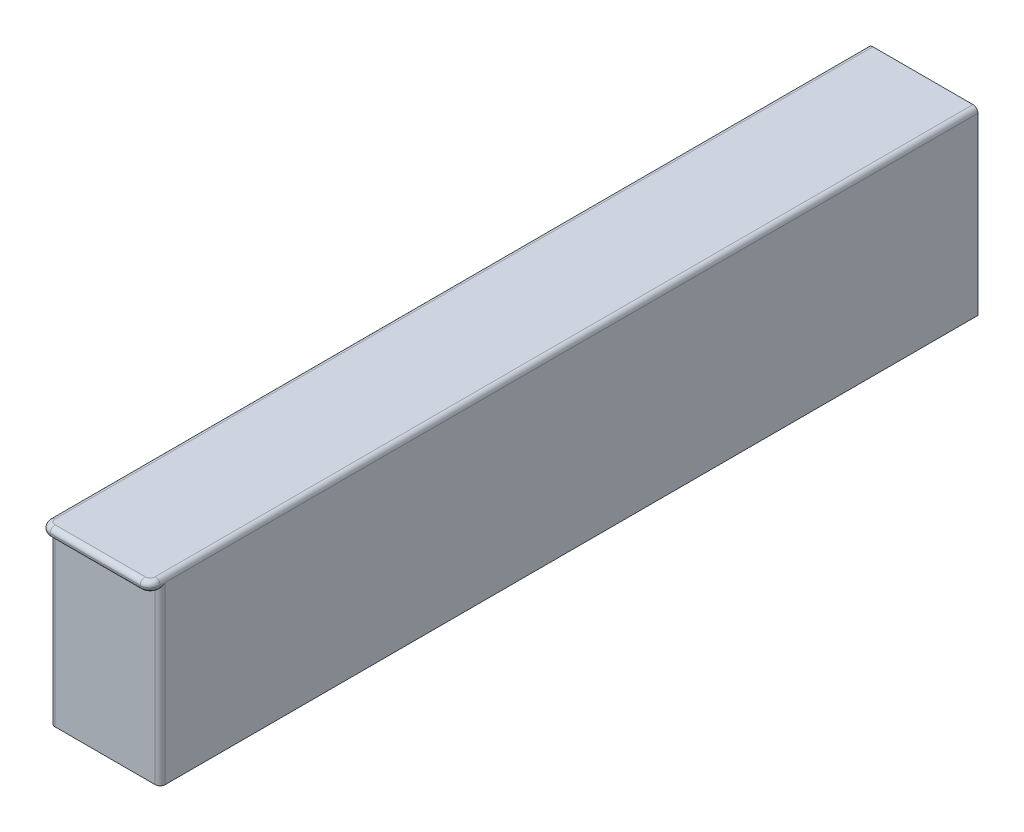
SolidWorks part; units mm, degrees
ref_plane "Front Plane" through (0, 0, 0) normal (0, 0, 1) x (1, 0, 0)
ref_plane "Top Plane" through (0, 0, 0) normal (0, 1, 0) x (1, 0, 0)
ref_plane "Right Plane" through (0, 0, 0) normal (1, 0, 0) x (0, 0, -1)
sketch "Sketch1" plane through (0, 0, 0) normal (0, 1, 0) x (1, 0, 0)
  line L1 (-11, -81.75) -> (11, -81.75)
  line L2 (-11, -81.75) -> (-11, 81.75)
  line L3 (-11, 81.75) -> (11, 81.75)
  line L4 (11, -81.75) -> (11, 81.75)
  line L5 (-11, -81.75) -> (11, 81.75) construction
  line L6 (-11, 81.75) -> (11, -81.75) construction
  point P0 (0, 0)
  dimension "D1" = 163.5
  dimension "D2" = 22
extrude "Boss-Extrude1" add sketch "Sketch1" along normal blind 36 contours L2 L3 L4 L1
fillet "Fillet1" radius 1 2 edges at (-11, 18, 81.75) (11, 18, 81.75)
sketch "Sketch2" plane through (0, 36, 0) normal (0, 1, 0) x (1, 0, 0)
  line L0 (11, -80.75) -> (11, 81.75) construction
  line L1 (-11, 81.75) -> (11, 81.75)
  line L2 (-11, 81.75) -> (-11, -83.75)
  line L3 (-11, -83.75) -> (11, -83.75)
  line L4 (11, 81.75) -> (11, -83.75)
  line L5 (-10, -81.75) -> (10, -81.75) construction
  dimension "D1" = 2
extrude "Boss-Extrude2" add sketch "Sketch2" against normal blind 2
fillet "Fillet2" radius 2 2 edges at (-11, 35, 83.75) (11, 35, 83.75)
fillet "Fillet3" radius 1 10 edges at (-11, 34, 81.25) (-10.4142, 34, 83.1642) (11, 34, 81.25) (10.4142, 34, 83.1642) (11, 36, 0) (10.4142, 36, 83.1642) (0, 36, 83.75) (-10.4142, 36, 83.1642) (-11, 36, 0) (0, 34, 83.75)
sketch "Sketch3" plane through (0, 36, 0) normal (0, 1, 0) x (1, 0, 0)
  line L1 (7.5, -31.75) -> (11, -31.75)
  line L2 (7.5, -31.75) -> (7.5, 81.75)
  line L3 (7.5, 81.75) -> (11, 81.75)
  line L4 (11, -31.75) -> (11, 81.75)
  line L5 (7.5, -31.75) -> (11, 81.75) construction
  line L6 (7.5, 81.75) -> (11, -31.75) construction
  line L7 (-10, -81.75) -> (10, -81.75) construction
  line L8 (-11, 81.75) -> (11, 81.75) construction
  line L9 (11, 81.75) -> (11, -80.75) construction
  dimension "D1" = 3.5
  dimension "D2" = 50
extrude "Cut-Extrude2" [suppressed] cut sketch "Sketch3" against normal through all
sketch "Sketch5" plane through (-11, 0, 0) normal (-1, 0, 0) x (0, 0, 1)
  line L0 (81.75, 34) -> (81.75, 0) construction
  line L1 (80.75, 0) -> (-81.75, 0) construction
  line L2 (-81.75, 36) -> (81.75, 36) construction
  line L3 (-81.75, 35) -> (-81.75, 0) construction
  line L8 (31.75, 36) -> (-81.75, 36)
  line L9 (31.75, 0) -> (31.75, 36)
  line L10 (-81.75, 0) -> (31.75, 0)
  line L11 (-81.75, 36) -> (-81.75, 0)
  dimension "D1" = 50
extrude "Cut-Extrude4" [suppressed] cut sketch "Sketch5" against normal blind 3.5
sketch "Sketch4" [suppressed] plane through (7.5, 0, 0) normal (1, 0, 0) x (0, 0, -1)
  line L4 (81.75, 36) -> (-31.75, 36)
  line L5 (-31.75, 36) -> (-31.75, 0)
  line L6 (-31.75, 0) -> (81.75, 0)
  line L7 (81.75, 0) -> (81.75, 36)
  line L8 (81.75, 36) -> (-31.75, 36)
  line L9 (-31.75, 36) -> (-31.75, 0)
  line L10 (-31.75, 0) -> (81.75, 0)
  line L11 (81.75, 0) -> (81.75, 36)
  dimension "D1" = 0
extrude "Cut-Extrude3" [suppressed] cut sketch "Sketch4" against normal blind 3.25
sketch "Sketch6" [suppressed] plane through (-7.5, 0, 0) normal (-1, 0, 0) x (0, 0, 1)
  line L4 (-81.75, 36) -> (-81.75, 0)
  line L5 (-81.75, 0) -> (31.75, 0)
  line L6 (31.75, 0) -> (31.75, 36)
  line L7 (31.75, 36) -> (-81.75, 36)
  line L8 (-81.75, 36) -> (-81.75, 0)
  line L9 (-81.75, 0) -> (31.75, 0)
  line L10 (31.75, 0) -> (31.75, 36)
  line L11 (31.75, 36) -> (-81.75, 36)
  dimension "D1" = 0
extrude "Cut-Extrude5" [suppressed] cut sketch "Sketch6" against normal blind 3.25
sketch "White" plane through (0, 0, 0) normal (0, 1, 0) x (1, 0, 0)
  line L0 (12.5, -81.75) -> (34.5, -81.75)
  line L1 (-11, -81.75) -> (11, -81.75)
  line L2 (-11, -81.75) -> (-11, 81.75)
  line L3 (-11, 81.75) -> (11, 81.75)
  line L4 (11, -81.75) -> (11, 81.75)
  line L5 (12.5, -81.75) -> (12.5, 81.75)
  line L6 (12.5, 81.75) -> (34.5, 81.75)
  line L7 (34.5, -81.75) -> (34.5, 81.75)
  line L8 (36, -81.75) -> (58, -81.75)
  line L9 (36, -81.75) -> (36, 81.75)
  line L10 (36, 81.75) -> (58, 81.75)
  line L11 (58, -81.75) -> (58, 81.75)
  line L12 (59.5, -81.75) -> (81.5, -81.75)
  line L13 (59.5, -81.75) -> (59.5, 81.75)
  line L14 (59.5, 81.75) -> (81.5, 81.75)
  line L15 (81.5, -81.75) -> (81.5, 81.75)
  line L16 (83, -81.75) -> (105, -81.75)
  line L17 (83, -81.75) -> (83, 81.75)
  line L18 (83, 81.75) -> (105, 81.75)
  line L19 (105, -81.75) -> (105, 81.75)
  line L20 (106.5, -81.75) -> (128.5, -81.75)
  line L21 (106.5, -81.75) -> (106.5, 81.75)
  line L22 (106.5, 81.75) -> (128.5, 81.75)
  line L23 (128.5, -81.75) -> (128.5, 81.75)
  line L24 (130, -81.75) -> (152, -81.75)
  line L25 (130, -81.75) -> (130, 81.75)
  line L26 (130, 81.75) -> (152, 81.75)
  line L27 (152, -81.75) -> (152, 81.75)
  dimension "D1" = 7
sketch "Black" plane through (0, 0, 0) normal (0, 1, 0) x (1, 0, 0)
  line L0 (-11, 81.75) -> (11, 81.75) construction
  line L1 (16, -31.75) -> (4, -31.75)
  line L2 (16, -31.75) -> (16, 81.75)
  line L3 (16, 81.75) -> (4, 81.75)
  line L4 (4, -31.75) -> (4, 81.75)
  line L6 (31, -31.75) -> (43, -31.75)
  line L7 (31, -31.75) -> (31, 81.75)
  line L8 (31, 81.75) -> (43, 81.75)
  line L9 (43, -31.75) -> (43, 81.75)
  line L10 (12.5, -81.75) -> (34.5, -81.75) construction
  line L11 (16, -31.75) -> (31, -31.75) construction
  line L12 (36, 81.75) -> (58, 81.75) construction
  line L13 (106.5, 81.75) -> (128.5, 81.75) construction
  line L14 (111.75, 81.75) -> (99.75, 81.75)
  line L15 (111.75, 81.75) -> (111.75, -31.75)
  line L16 (111.75, -31.75) -> (99.75, -31.75)
  line L17 (99.75, 81.75) -> (99.75, -31.75)
  line L18 (83, 81.75) -> (105, 81.75) construction
  line L19 (126.75, 81.75) -> (138.75, 81.75)
  line L20 (126.75, 81.75) -> (126.75, -31.75)
  line L21 (126.75, -31.75) -> (138.75, -31.75)
  line L22 (138.75, 81.75) -> (138.75, -31.75)
  line L23 (84.75, 81.75) -> (72.75, 81.75)
  line L24 (84.75, 81.75) -> (84.75, -31.75)
  line L25 (84.75, -31.75) -> (72.75, -31.75)
  line L26 (72.75, 81.75) -> (72.75, -31.75)
  line L27 (105, -81.75) -> (106.5, -81.75) construction
  point P14 (23.5, -81.75)
  point P15 (23.5, -31.75)
  point P36 (105.75, -81.75)
  point P37 (105.75, -31.75)
  dimension "D1" = 50
  dimension "D2" = 12
  dimension "D3" = 12
  dimension "D4" = 15
  dimension "D5" = 15
  dimension "D6" = 15
sketch "Sketch11" plane through (0, 36, 0) normal (0, 1, 0) x (1, 0, 0)
  line L1 (11, 81.75) -> (2.5, 81.75)
  line L2 (11, 81.75) -> (11, -31.75)
  line L3 (11, -31.75) -> (2.5, -31.75)
  line L4 (2.5, 81.75) -> (2.5, -31.75)
  line L5 (16, -31.75) -> (4, -31.75) construction
  dimension "D1" = 8.5
extrude "C" [suppressed] cut sketch "Sketch11" against normal through all
sketch "Sketch12" plane through (0, 36, 0) normal (0, 1, 0) x (1, 0, 0)
  line L0 (31, -31.75) -> (43, -31.75) construction
  line L1 (-11, 81.75) -> (-6, 81.75)
  line L2 (-11, 81.75) -> (-11, -31.75)
  line L3 (-11, -31.75) -> (-6, -31.75)
  line L4 (-6, 81.75) -> (-6, -31.75)
  line L5 (11, 81.75) -> (6, 81.75)
  line L6 (11, 81.75) -> (11, -31.75)
  line L7 (11, -31.75) -> (6, -31.75)
  line L8 (6, 81.75) -> (6, -31.75)
  dimension "D1" = 5
  dimension "D2" = 5
extrude "D" [suppressed] cut sketch "Sketch12" against normal through all
sketch "Sketch13" plane through (0, 36, 0) normal (0, 1, 0) x (1, 0, 0)
  line L1 (-11, 81.75) -> (-2.5, 81.75)
  line L2 (-11, 81.75) -> (-11, -31.75)
  line L3 (-11, -31.75) -> (-2.5, -31.75)
  line L4 (-2.5, 81.75) -> (-2.5, -31.75)
  line L5 (16, -31.75) -> (4, -31.75) construction
  dimension "D1" = 8.5
extrude "E" [suppressed] cut sketch "Sketch13" against normal through all
sketch "Sketch14" plane through (0, 36, 0) normal (0, 1, 0) x (1, 0, 0)
  line L0 (16, -31.75) -> (4, -31.75) construction
  line L1 (11, 81.75) -> (0.75, 81.75)
  line L2 (11, 81.75) -> (11, -31.75)
  line L3 (11, -31.75) -> (0.75, -31.75)
  line L4 (0.75, 81.75) -> (0.75, -31.75)
  dimension "D1" = 10.25
extrude "F" [suppressed] cut sketch "Sketch14" against normal through all
sketch "Sketch15" plane through (0, 36, 0) normal (0, 1, 0) x (1, 0, 0)
  line L1 (-11, 81.75) -> (-7.75, 81.75)
  line L2 (-11, 81.75) -> (-11, -31.75)
  line L3 (-11, -31.75) -> (-7.75, -31.75)
  line L4 (-7.75, 81.75) -> (-7.75, -31.75)
  line L5 (11, 81.75) -> (4.25, 81.75)
  line L6 (11, 81.75) -> (11, -31.75)
  line L7 (11, -31.75) -> (4.25, -31.75)
  line L8 (4.25, 81.75) -> (4.25, -31.75)
  line L9 (16, -31.75) -> (4, -31.75) construction
  dimension "D1" = 3.25
  dimension "D2" = 6.75
extrude "G" [suppressed] cut sketch "Sketch15" against normal through all
sketch "Sketch16" plane through (0, 36, 0) normal (0, 1, 0) x (1, 0, 0)
  line L0 (16, -31.75) -> (4, -31.75) construction
  line L1 (-11, 81.75) -> (-4.25, 81.75)
  line L2 (-11, 81.75) -> (-11, -31.75)
  line L3 (-11, -31.75) -> (-4.25, -31.75)
  line L4 (-4.25, 81.75) -> (-4.25, -31.75)
  line L5 (11, 81.75) -> (7.75, 81.75)
  line L6 (11, 81.75) -> (11, -31.75)
  line L7 (11, -31.75) -> (7.75, -31.75)
  line L8 (7.75, 81.75) -> (7.75, -31.75)
  dimension "D1" = 6.75
  dimension "D2" = 3.25
extrude "A" [suppressed] cut sketch "Sketch16" against normal through all
sketch "Sketch17" plane through (0, 36, 0) normal (0, 1, 0) x (1, 0, 0)
  line L0 (16, -31.75) -> (4, -31.75) construction
  line L1 (-11, 81.75) -> (-0.75, 81.75)
  line L2 (-11, 81.75) -> (-11, -31.75)
  line L3 (-11, -31.75) -> (-0.75, -31.75)
  line L4 (-0.75, 81.75) -> (-0.75, -31.75)
  dimension "D1" = 10.25
extrude "B" [suppressed] cut sketch "Sketch17" against normal through all
